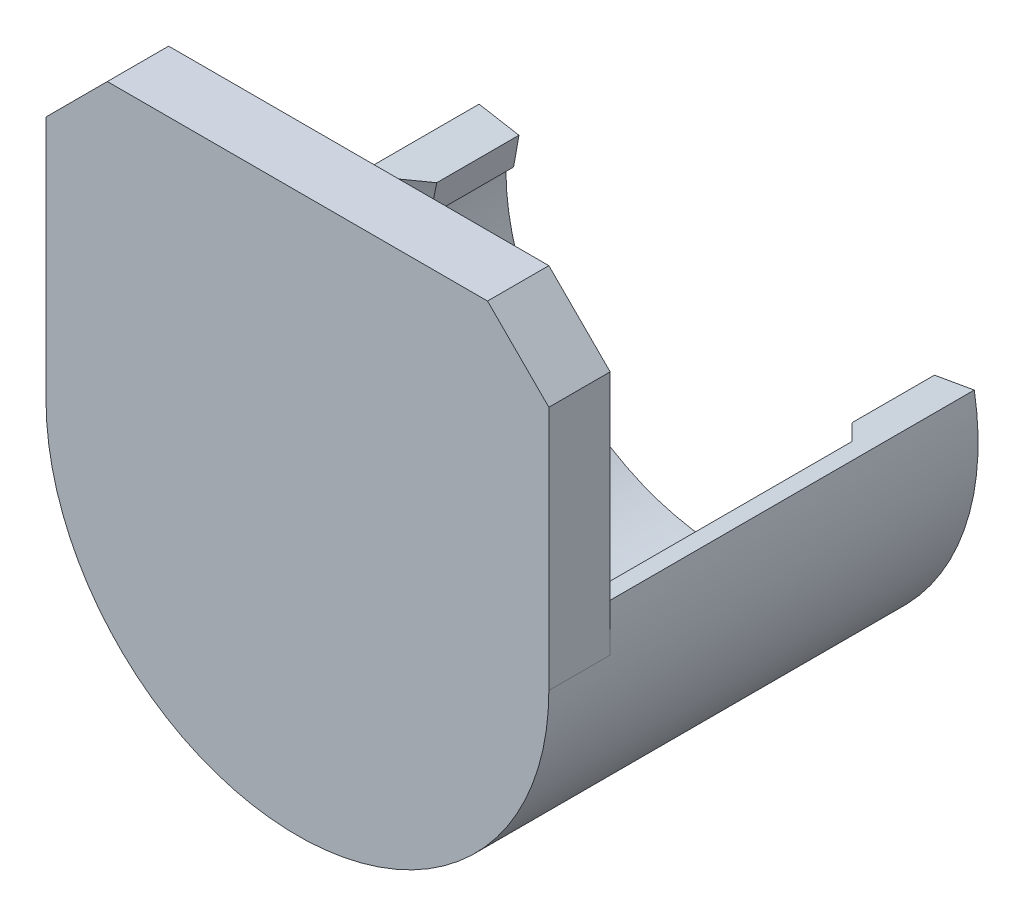
SolidWorks part; units mm, degrees
material "PET"
ref_plane "Front Plane" through (0, 0, 0) normal (0, 0, 1) x (1, 0, 0)
ref_plane "Top Plane" through (0, 0, 0) normal (0, 1, 0) x (1, 0, 0)
ref_plane "Right Plane" through (0, 0, 0) normal (1, 0, 0) x (0, 0, -1)
sketch "Sketch1" plane through (0, 0, 0) normal (0, 0, 1) x (1, 0, 0)
  line L0 (0, 0) -> (-11.2564, 1.9848) construction
  line L1 (-11.2564, 1.9848) -> (-12.8197, 2.2605)
  line L2 (0, 0) -> (0, -13.0175) construction
  line L3 (11.2564, 1.9848) -> (12.8197, 2.2605)
  line L4 (-11.2564, 1.9848) -> (-10.7561, 1.8966)
  line L5 (-10.7561, 1.8966) -> (-11.0317, 0.3332)
  line L6 (-11.0317, 0.3332) -> (-11.43, 0)
  line L7 (11.0317, 0.3332) -> (11.43, 0)
  line L8 (10.7561, 1.8966) -> (11.0317, 0.3332)
  line L9 (11.2564, 1.9848) -> (10.7561, 1.8966)
  arc A0 (-11.43, 0) -> (11.43, 0) centre (0, 0) ccw
  arc A1 (-12.8197, 2.2605) -> (12.8197, 2.2605) centre (0, 0) ccw
  arc A2 (11.2564, 1.9848) -> (-11.2564, 1.9848) centre (0, 0) ccw construction
  arc A3 (12.8197, 2.2605) -> (-12.8197, 2.2605) centre (0, 0) ccw construction
  dimension "D1" = 22.86
  dimension "D2" = 1.5875
  dimension "D3" = 100
  dimension "D4" = 0.508
  dimension "D5" = 1.5875
extrude "Boss-Extrude1" add sketch "Sketch1" along normal blind 19.05
sketch "Sketch3" plane through (0, 0, 19.05) normal (0, 0, 1) x (1, 0, 0)
  circle A0 centre (0, 0) radius 13.0175
extrude "Boss-Extrude2" add sketch "Sketch3" along normal blind 3.175
sketch "Sketch4" plane through (0, 0, 19.05) normal (0, 0, -1) x (-1, 0, 0)
  circle A0 centre (0, 0) radius 11.43
extrude "Cut-Extrude1" cut sketch "Sketch4" along normal offset from surface (15.875 mm away) 3.175 up to face at (0, -2.2159, 0)
chamfer "Chamfer1" distance 1.5875 angle 45 2 edges at (11.3865, 0.9962, 3.175) (-11.3865, 0.9962, 3.175)
chamfer "Chamfer2" distance 0.5292 angle 45 2 edges at (11.2564, 1.9848, 11.9063) (-11.2564, 1.9848, 11.9063)
sketch "Sketch5" plane through (0, 0, 22.225) normal (0, 0, 1) x (1, 0, 0)
  line L1 (13.0175, 0) -> (-13.0175, 0)
  line L2 (13.0175, 0) -> (13.0175, 15.875)
  line L3 (13.0175, 15.875) -> (-13.0175, 15.875)
  line L4 (-13.0175, 0) -> (-13.0175, 15.875)
  circle A0 centre (0, 0) radius 13.0175 construction
  dimension "D1" = 15.875
extrude "Boss-Extrude3" add sketch "Sketch5" against normal up to surface (3.175 mm away) up to face at (0, 1.575, 19.05)
chamfer "Chamfer3" distance 3.175 angle 45 2 edges at (-13.0175, 15.875, 20.6375) (13.0175, 15.875, 20.6375)
